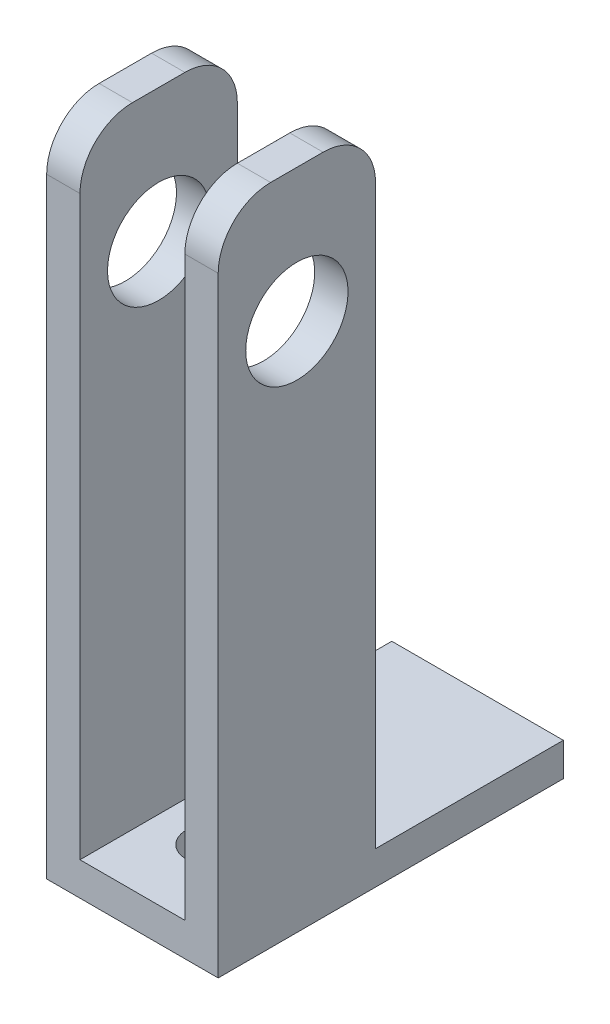
SolidWorks part; units mm, degrees
ref_plane "Front Plane" through (0, 0, 0) normal (0, 0, 1) x (1, 0, 0)
ref_plane "Top Plane" through (0, 0, 0) normal (0, 1, 0) x (1, 0, 0)
ref_plane "Right Plane" through (0, 0, 0) normal (1, 0, 0) x (0, 0, -1)
sketch "Sketch1" plane through (0, 0, 0) normal (0, 1, 0) x (1, 0, 0)
  circle A0 centre (0, 0) radius 10
  dimension "D1" = 20
extrude "Boss-Extrude1" add sketch "Sketch1" along normal blind 6.35
sketch "Sketch5" plane through (0, 6.35, 0) normal (0, 1, 0) x (1, 0, 0)
  line L27 (0, 15) -> (0, -15) construction
  line L28 (-10, 15) -> (10, 15)
  line L29 (-10, 15) -> (-10, -15)
  line L30 (-10, -15) -> (10, -15)
  line L31 (10, 15) -> (10, -15)
  line L32 (-10, 0) -> (10, 0) construction
  point P0 (0, 0)
  dimension "D1" = 20
  dimension "D2" = 30
extrude "Boss-Extrude2" add sketch "Sketch5" against normal blind 6.35
sketch "Sketch7" plane through (0, 6.35, 0) normal (0, 1, 0) x (1, 0, 0)
  line L13 (0, 0) -> (0, 21) construction
  line L29 (-16.35, 15) -> (-10, 15)
  line L30 (-16.35, 15) -> (-16.35, -15)
  line L31 (-16.35, -15) -> (-10, -15)
  line L32 (-10, 15) -> (-10, -15)
  line L38 (10, 15) -> (10, -15)
  line L39 (16.35, -15) -> (10, -15)
  line L40 (16.35, 15) -> (16.35, -15)
  line L41 (16.35, 15) -> (10, 15)
  circle A0 centre (0, 0) radius 38 construction
  point P9 (0, 0)
  dimension "D1" = 6.35
  dimension "D2" = 30
extrude "Boss-Extrude3" add sketch "Sketch7" along normal blind 120 and the other way blind 6.35
sketch "Sketch8" plane through (-16.35, 0, 0) normal (-1, 0, 0) x (0, 0, 1)
  line L4 (-15, 126.35) -> (15, 126.35) construction
  line L5 (0, 126.35) -> (0, 0) construction
  line L6 (-15, 126.35) -> (15, 126.35) construction
  line L7 (-15, 0) -> (15, 0) construction
  circle A0 centre (0, 100.95) radius 9.75
  point P8 (0, 0)
  dimension "D1" = 19.5
  dimension "D2" = 25.4
extrude "Cut-Extrude2" cut sketch "Sketch8" against normal through all
sketch "Sketch2" plane through (0, 6.35, 0) normal (0, 1, 0) x (1, 0, 0)
  circle A0 centre (0, 0) radius 4.7625
  dimension "D1" = 9.525
extrude "Cut-Extrude1" cut sketch "Sketch2" against normal through all
fillet "Fillet2" radius 10 4 edges at (13.175, 126.35, -15) (-13.175, 126.35, 15) (13.175, 126.35, 15) (-13.175, 126.35, -15)
sketch "Sketch11" plane through (0, 0, 0) normal (0, -1, 0) x (1, 0, 0)
  line L1 (-16.35, -15) -> (16.35, -15)
  line L2 (-16.35, -15) -> (-16.35, -50.8)
  line L3 (-16.35, -50.8) -> (16.35, -50.8)
  line L4 (16.35, -15) -> (16.35, -50.8)
  dimension "D1" = 35.8
extrude "Boss-Extrude5" add sketch "Sketch11" against normal blind 6.35
